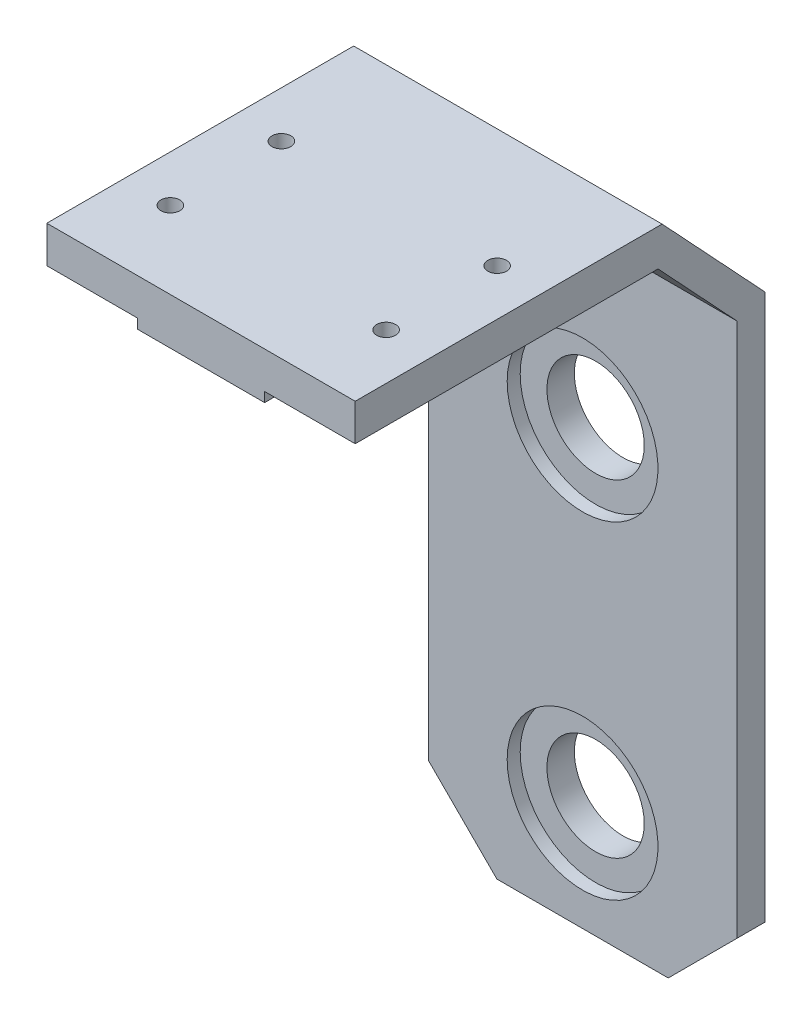
SolidWorks part; units mm, degrees
material "PLA"
ref_plane "Front Plane" through (0, 0, 0) normal (0, 0, 1) x (1, 0, 0)
ref_plane "Top Plane" through (0, 0, 0) normal (0, 1, 0) x (1, 0, 0)
ref_plane "Right Plane" through (0, 0, 0) normal (1, 0, 0) x (0, 0, -1)
sketch "Sketch1" plane through (0, 0, 0) normal (0, 0, 1) x (1, 0, 0)
  line L0 (0, -28.15) -> (0, 19.65) construction
  line L1 (-22.5, -44) -> (22.5, -44)
  line L2 (-22.5, -44) -> (-22.5, 42)
  line L3 (-22.5, 42) -> (22.5, 42)
  line L4 (22.5, -44) -> (22.5, 42)
  line L5 (0, 19.65) -> (22.5, 19.65) construction
  circle A0 centre (0, 19.65) radius 7.1
  circle A1 centre (0, -28.15) radius 7.1
  point P8 (0, 42)
  dimension "D3" = 14.2
  dimension "D4" = 14.2
  dimension "D1" = 45
  dimension "D2" = 86
  dimension "D5" = 47.8
extrude "Boss-Extrude1" add sketch "Sketch1" along normal blind 4
sketch "Sketch2" plane through (22.5, 0, 0) normal (1, 0, 0) x (0, 0, -1)
  line L0 (-4, 42) -> (-17.386, 56.3434)
  line L1 (-18.3995, 61.7155) -> (0, 42)
  line L2 (-4, 42) -> (0, 42)
  spline S0 degree 3 poles (-2014.4324, -19.1061) (19.3209, 136.6863) (-24.8796, 92.8702) (-17.0596, 54.6043) (-17.0529, 54.5296) (-17.0533, 53.872) (-17.0538, 47.5105) (-17.0544, 40.908) (-17.0552, 34.8675) (-17.0525, 34.563) (-17.0625, 34.3936) (-28.231, -39.593) (-1.5149, -116.9494) (-2012.287, -34.5153) knots -0.881536 -0.881536 -0.881536 -0.881536 0.129883 0.131348 0.131456 0.131836 0.148438 0.296875 0.304199 0.304688 0.304742 0.308594 2.23779 2.23779 2.23779 2.23779 only from (-17.0859, 54.7337) to (-17.6041, 30.65) construction
  spline S1 degree 3 poles (-18.3995, 61.7155) (-17.9641, 59.933) (-17.6988, 58.1353) (-17.386, 56.3434) knots 0.068293 0.068293 0.068293 0.068293 0.115576 0.115576 0.115576 0.115576
extrude "Boss-Extrude2" add sketch "Sketch2" against normal up to surface (45 mm away) up to face at (-22.5, -1, 2)
ref_plane "Plane1" through (0, 0, 18.28) normal (0, 0, 1) x (1, 0, 0)
sketch "Sketch3" plane through (0, 0, 18.28) normal (0, 0, 1) x (1, 0, 0)
  line L2 (-22.5, 56.3434) -> (22.5, 56.3434)
  line L3 (22.5, 61.7155) -> (-22.5, 61.7155)
  line L4 (-22.5, 56.3434) -> (22.5, 56.3434)
  line L5 (22.5, 61.7155) -> (-22.5, 61.7155)
  line L8 (-22.5, 61.7155) -> (-22.5, 56.3434)
  line L9 (-22.5, 61.7155) -> (-22.5, 56.3434)
  line L10 (22.5, 56.3434) -> (22.5, 61.7155)
  line L11 (22.5, 56.3434) -> (22.5, 61.7155)
  dimension "D1" = 0
extrude "Boss-Extrude3" add sketch "Sketch3" along normal blind 40 and the other way up to surface other way up to face at (0, 59.0295, 17.8927)
sketch "Sketch4" plane through (0, 0, 58.28) normal (0, 0, 1) x (1, 0, 0)
  line L2 (-22.5, 56.3434) -> (22.5, 56.3434)
  line L3 (22.5, 61.7155) -> (-22.5, 61.7155)
  line L4 (-22.5, 56.3434) -> (22.5, 56.3434)
  line L5 (22.5, 61.7155) -> (-22.5, 61.7155)
  spline S2 degree 1 poles (-22.5, 3061.698) (-22.5, -2943.6427) knots -558.436423 -558.436423 559.437101 559.437101 only from (-22.5, 61.7155) to (-22.5, 56.3434)
  spline S3 degree 1 poles (22.5, -2943.6391) (22.5, 3061.7016) knots -558.436423 -558.436423 559.437101 559.437101 only from (22.5, 56.3434) to (22.5, 61.7155)
  spline S4 degree 1 poles (-22.5, 61.7155) (-22.5, 56.3434) knots 0 0 1 1
  spline S5 degree 1 poles (22.5, 56.3434) (22.5, 61.7155) knots 0 0 1 1
  dimension "D1" = 0
extrude "Boss-Extrude4" add sketch "Sketch4" along normal up to surface (3.295 mm away)
sketch "Sketch5" plane through (0, 0, 61.575) normal (0, 0, 1) x (1, 0, 0)
  line L0 (22.5, 56.3434) -> (-22.5, 56.3434) construction
  line L2 (-9.493, 56.2434) -> (-9.493, 56.3434) construction
  line L3 (-9.493, 56.3434) -> (9.4868, 56.3434) construction
  line L4 (9.4868, 56.2434) -> (9.4868, 56.3434) construction
  line L6 (-9.293, 56.3434) -> (9.2868, 56.3434)
  line L7 (-9.293, 56.3434) -> (-9.293, 54.9337)
  line L8 (-9.293, 54.9337) -> (9.2868, 54.9337)
  line L9 (9.2868, 56.3434) -> (9.2868, 54.9337)
  dimension "D1" = 0.2
  dimension "D2" = 0.2
extrude "Boss-Extrude5" add sketch "Sketch5" against normal up to vertex (44.189 mm away) up to point (-22.5, 56.3434, 17.386)
chamfer "Chamfer2" distance 1.405 angle 45 1 edges at (-0.0031, 54.9337, 17.386)
sketch "Sketch7" plane through (22.5, 0, 0) normal (1, 0, 0) x (0, 0, -1)
  line L0 (-18.28, 61.7155) -> (-16.7937, 61.7155)
  line L1 (-16.7937, 61.7155) -> (0, 43.7206)
  line L2 (0, 42) -> (-18.28, 61.5875) construction
  line L3 (0, 42) -> (0, 43.7206)
  line L4 (-18.28, 61.7155) -> (-18.28, 61.5875)
  line L5 (-18.28, 61.5875) -> (0, 42)
extrude "Boss-Extrude7" add sketch "Sketch7" against normal up to surface (45 mm away) up to face at (-22.5, 32.6339, 20.5662)
sketch "Sketch8" plane through (0, 61.7155, 0) normal (0, 1, 0) x (1, 0, 0)
  circle A0 centre (15.735, -50.299) radius 1.375 construction
  circle A1 centre (15.735, -34.0971) radius 1.375 construction
  circle A2 centre (-15.743, -34.0971) radius 1.375 construction
  circle A3 centre (-15.743, -50.299) radius 1.375 construction
  circle A4 centre (15.735, -50.299) radius 1.375
  circle A5 centre (15.735, -34.0971) radius 1.375
  circle A6 centre (-15.743, -34.0971) radius 1.375
  circle A7 centre (-15.743, -50.299) radius 1.375
extrude "Cut-Extrude1" cut sketch "Sketch8" against normal through all
chamfer "Chamfer3" distance 10 angle 45 2 edges at (22.5, -44, 2) (-22.5, -44, 2)
chamfer "Chamfer4" distance 1.75 angle 45 5 edges at (-22.5, 4.8603, 0) (-17.5, -39, 0) (0, -44, 0) (17.5, -39, 0) (22.5, 4.8603, 0)
sketch "Sketch9" plane through (0, 0, 4) normal (0, 0, 1) x (1, 0, 0)
  line L1 (-22.5, 46.4753) -> (22.5, 46.4753)
  line L2 (-22.5, 46.4753) -> (-22.5, -34)
  line L6 (12.5, -44) -> (22.5, -34) construction
  line L7 (-12.5, -44) -> (12.5, -44) construction
  line L8 (-22.5, -34) -> (-12.5, -44) construction
  line L9 (12.5, -44) -> (22.5, -34)
  line L10 (-12.5, -44) -> (12.5, -44)
  line L11 (-22.5, -34) -> (-12.5, -44)
  line L12 (22.5, 46.4753) -> (22.5, -34)
  circle A0 centre (0, 19.65) radius 11
  circle A1 centre (0, -28.15) radius 11
  line M9 (-12.5, -44) -> (12.5, -44)
  line M10 (12.5, -44) -> (22.5, -34)
  line M11 (22.5, -34) -> (22.5, 42)
  line M12 (22.5, 42) -> (-22.5, 42)
  line M13 (-22.5, 42) -> (-22.5, -34)
  line M14 (-22.5, -34) -> (-12.5, -44)
  dimension "D2" = 22
  dimension "D3" = 22
extrude "Boss-Extrude8" add sketch "Sketch9" along normal blind 1.9 contours A1 A0 M14 M9 M10 M11 M12 M13 | L12 L1 L2 M12 region at (0, 44.2376, 4) region at (0, 1.1389, 4)
